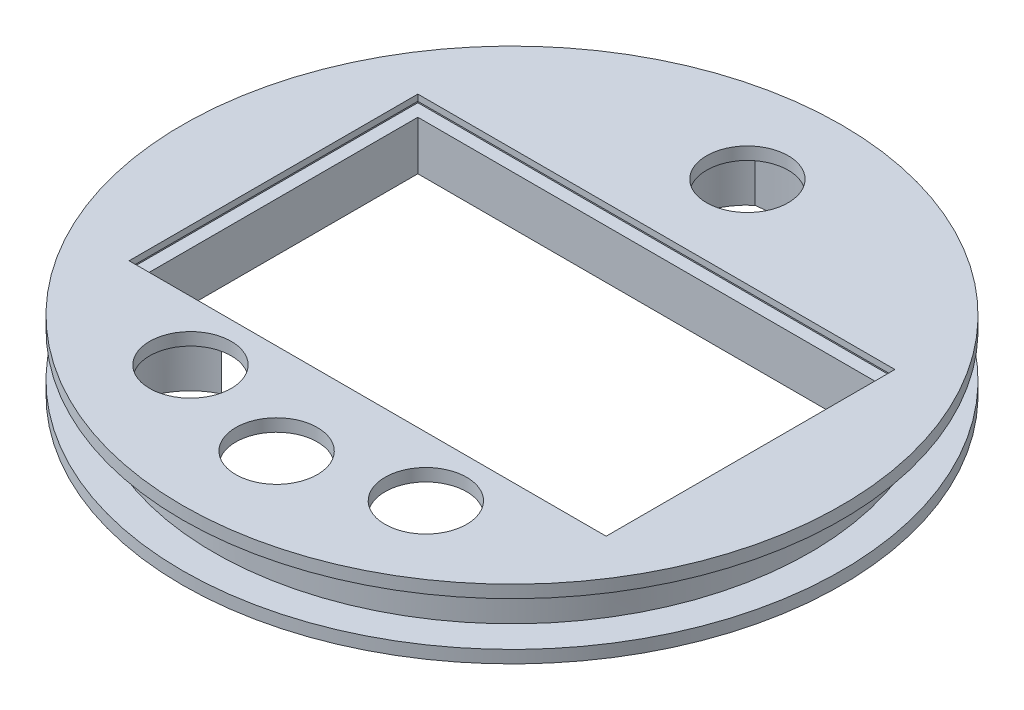
SolidWorks part; units mm, degrees
ref_plane "Front Plane" through (0, 0, 0) normal (0, 0, 1) x (1, 0, 0)
ref_plane "Top Plane" through (0, 0, 0) normal (0, 1, 0) x (1, 0, 0)
ref_plane "Right Plane" through (0, 0, 0) normal (1, 0, 0) x (0, 0, -1)
sketch "Sketch1" plane through (0, 0, 0) normal (0, 1, 0) x (1, 0, 0)
  line L0 (-18.75, -32.476) -> (0, 0)
  line L1 (0, 0) -> (18.75, -32.476)
  line L3 (-38, -23) -> (38, -23)
  line L4 (-38, -23) -> (-38, 23)
  line L5 (-38, 23) -> (38, 23)
  line L6 (38, -23) -> (38, 23)
  line L7 (-38, -23) -> (38, 23) construction
  line L8 (-38, 23) -> (38, -23) construction
  circle A0 centre (0, 0) radius 47.5
  circle A1 centre (0, 37.5) radius 6.5
  circle A2 centre (0, -37.5) radius 6.5
  circle A3 centre (18.75, -32.476) radius 6.5
  circle A4 centre (-18.75, -32.476) radius 6.5
  circle A5 centre (0, 0) radius 37.5 construction
  circle A6 centre (0, -37.5) radius 8 construction
  circle A7 centre (-18.75, -32.476) radius 8 construction
  point P18 (20, -34.641)
  dimension "D2" = 13
  dimension "D3" = 75
  dimension "D4" = 95
  dimension "D5" = 16
  dimension "D1" = 60
  dimension "D6" = 46
  dimension "D7" = 76
extrude "Boss-Extrude1" add sketch "Sketch1" along normal mid plane 2 contours A0 A4 A3 A2 A1 region at (-46.1565, 0, 0)
sketch "Sketch2" plane through (0, -1, 0) normal (0, -1, 0) x (1, 0, 0)
  circle A0 centre (0, 0) radius 47.5 construction
  circle A1 centre (0, 0) radius 47.5
  circle A2 centre (0, 0) radius 46
  circle A4 centre (0, -37.5) radius 6.5 construction
  point P0 (0, -44)
  point P6 (0, -46)
  dimension "D1" = 2
extrude "Boss-Extrude2" add sketch "Sketch2" along normal blind 9
sketch "Sketch3" plane through (0, 1, 0) normal (0, 1, 0) x (1, 0, 0)
  circle A0 centre (0, 0) radius 47.5 construction
  circle A1 centre (0, 0) radius 47.5
  circle A2 centre (0, 0) radius 52.5
  dimension "D1" = 5
extrude "Boss-Extrude3" add sketch "Sketch3" against normal blind 2
extrude "Boss-Extrude4" add sketch "Sketch3<2>" along normal blind 2 from surface starting at face at (0, -10, -47.5)
sketch "Sketch3<2>" plane through (0, 1, 0) normal (0, 1, 0) x (1, 0, 0) same geometry as "Sketch3"
sketch "Sketch5" plane through (0, -1, 0) normal (0, -1, 0) x (1, 0, 0)
  line L1 (-38, 23) -> (-38, -23) construction
  line L2 (-38, -23) -> (38, -23) construction
  line L3 (38, 23) -> (38, -23) construction
  line L5 (-38, 23) -> (-38, -23)
  line L6 (-38, -23) -> (38, -23)
  line L7 (38, 23) -> (38, -23)
  line L8 (-38, 23) -> (38, 23) construction
  line L9 (23.2729, 23) -> (38, 23)
  line L10 (-23.2729, 23) -> (-38, 23)
  arc A0 (28.6431, 35.9941) -> (23.2729, 23) centre (18.75, 32.476) cw
  circle A1 centre (0, 0) radius 46
  circle A2 centre (0, 0) radius 46 construction
  arc A4 (-23.2729, 23) -> (-28.6431, 35.9941) centre (-18.75, 32.476) cw
  circle A5 centre (18.75, 32.476) radius 6.5 construction
  arc A6 (-6.8086, -45.4933) -> (6.8086, -45.4933) centre (0, -37.5) cw
  arc A7 (28.6431, 35.9941) -> (6.8086, -45.4933) centre (0, 0) cw
  arc A8 (-28.6431, 35.9941) -> (-6.8086, -45.4933) centre (0, 0) ccw
  dimension "D2" = 4
  dimension "D1" = 0
extrude "Boss-Extrude5" add sketch "Sketch5" along normal through all
sketch "Sketch4" plane through (0, 0, 0) normal (0, 1, 0) x (1, 0, 0)
  line L1 (-40, -25) -> (40, -25)
  line L2 (-40, -25) -> (-40, 25)
  line L3 (-40, 25) -> (40, 25)
  line L4 (40, -25) -> (40, 25)
  line L5 (-40, -25) -> (40, 25) construction
  line L6 (-40, 25) -> (40, -25) construction
  point P0 (0, 0)
  dimension "D1" = 50
  dimension "D2" = 80
extrude "Cut-Extrude1" cut sketch "Sketch4" against normal blind 2.2
